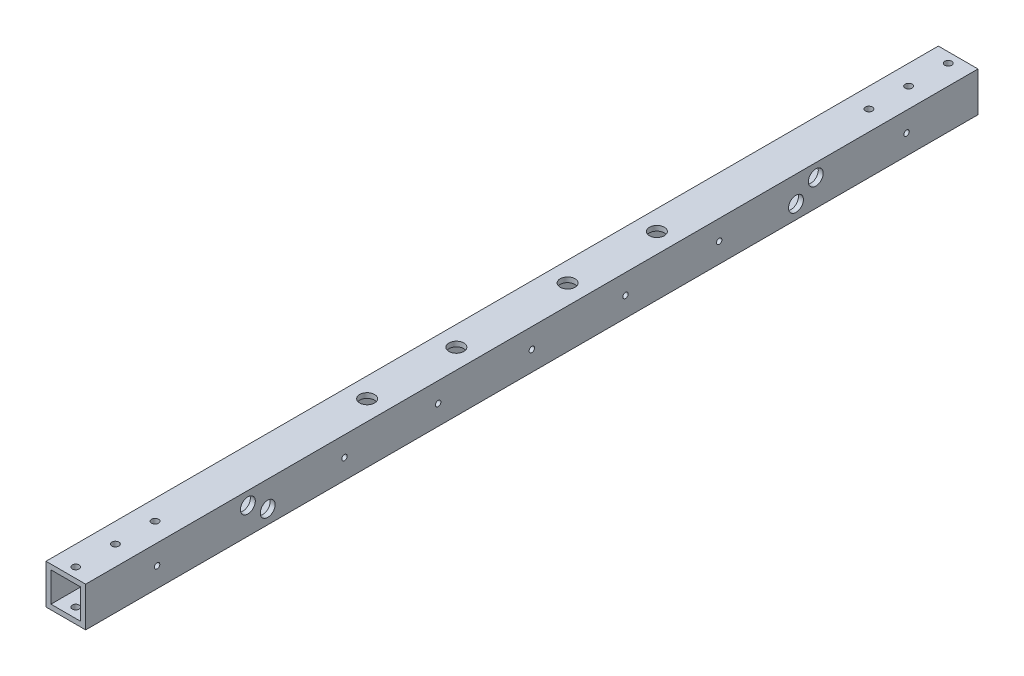
SolidWorks part; units mm, degrees
material "6061-T6 (SS)"
ref_plane "Front Plane" through (0, 0, 0) normal (0, 0, 1) x (1, 0, 0)
ref_plane "Top Plane" through (0, 0, 0) normal (0, 1, 0) x (1, 0, 0)
ref_plane "Right Plane" through (0, 0, 0) normal (1, 0, 0) x (0, 0, -1)
sketch "Sketch1" plane through (0, 0, 0) normal (0, 0, 1) x (1, 0, 0)
  line L1 (-12.7, -12.7) -> (12.7, -12.7)
  line L2 (-12.7, -12.7) -> (-12.7, 12.7)
  line L3 (-12.7, 12.7) -> (12.7, 12.7)
  line L4 (12.7, -12.7) -> (12.7, 12.7)
  line L5 (-12.7, -12.7) -> (12.7, 12.7) construction
  line L6 (-12.7, 12.7) -> (12.7, -12.7) construction
  point P0 (0, 0)
  dimension "D1" = 25.4
  dimension "D2" = 25.4
extrude "Extrude-Thin1" add sketch "Sketch1" along normal blind 571.5 thin thin type one direction reverse wall 3.175
hole_wizard "#8 Clearance Hole1" positions "3DSketch1" profile "Sketch3" hole size "#8" standard "ANSI Inch" end condition through all
sketch3d "3DSketch1"
  line L1 (12.7, 12.7, 0) -> (-12.7, 12.7, 0) construction
  line L6 (0, 12.7, 571.5) -> (0, 12.7, 0) construction
  line L7 (12.7, 12.7, 571.5) -> (-12.7, 12.7, 571.5) construction
  point P57 (0, 12.7, 6.35)
  point P59 (0, 12.7, 31.75)
  point P61 (0, 12.7, 57.15)
  point P63 (0, 12.7, 539.75)
  point P65 (0, 12.7, 514.35)
  point P67 (0, 12.7, 565.15)
  dimension "D1" = 25.4
  dimension "D2" = 25.4
  dimension "D3" = 6.35
  dimension "D4" = 25.4
  dimension "D5" = 25.4
  dimension "D6" = 6.35
sketch "Sketch3" plane through (0, 12.7, 565.15) normal (1, 0, 0) x (0, 0, 1)
  line L0 (0, 0) -> (0, 25.4)
  line L1 (0, 25.4) -> (2.2479, 25.4)
  line L2 (2.2479, 25.4) -> (2.2479, 0)
  line L5 (2.2479, 0) -> (0, 0)
  line L11 (0, -6.35) -> (0, 107.95) construction
  dimension "Thru Hole Dia." = 4.4958
  dimension "Thru Hole Depth" = 25.4
hole_wizard "#8-32 Tapped Hole1" positions "Sketch8" profile "Sketch9" tap size "#8-32" standard "ANSI Inch"
sketch "Sketch8" plane through (12.7, -82.55, 285.75) normal (1, 0, 0) x (0, 0, -1)
  point P0 (-240, 82.55)
  point P6 (-120, 82.55)
  point P9 (-60, 82.55)
  point P12 (0, 82.55)
  point P15 (60, 82.55)
  point P18 (120, 82.55)
  point P24 (240, 82.55)
sketch "Sketch9" plane through (12.7, 0, 525.75) normal (0, 1, 0) x (0, 0, -1)
  line L0 (0, 0) -> (0, 13.3314)
  line L1 (0, 13.3314) -> (1.7272, 12.2936)
  line L2 (1.7272, 12.2936) -> (1.7272, 0)
  line L3 (1.7272, 0) -> (0, 0)
  line L4 (0, 13.3314) -> (-1.7272, 12.2936) construction
  line L5 (0, -6.35) -> (0, 107.95) construction
  dimension "Tap Drill Dia." = 3.4544
  dimension "Tap Drill Depth" = 12.2936
  dimension "Drill Angle" = 118
hole_wizard "3/8 (0.375) Diameter Hole2" positions "Sketch12" profile "Sketch13" hole size "3/8" standard "ANSI Inch" end condition through all
sketch "Sketch12" plane through (-12.7, -82.55, 285.75) normal (1, 0, 0) x (0, 0, -1)
  point P0 (-181.864, 86.995)
  point P3 (-169.164, 78.74)
  point P6 (169.164, 78.74)
  point P9 (181.864, 86.995)
  point P12 (181.864, 57.15)
  point P15 (-181.864, 57.15)
sketch "Sketch13" plane through (-12.7, 4.445, 467.614) normal (0, 1, 0) x (0, 0, 1)
  line L0 (0, 0) -> (0, 25.4)
  line L1 (0, 25.4) -> (4.7625, 25.4)
  line L2 (4.7625, 25.4) -> (4.7625, 0)
  line L3 (4.7625, 0) -> (0, 0)
  line L4 (0, -6.35) -> (0, 107.95) construction
  dimension "Thru Hole Dia." = 9.525
  dimension "Thru Hole Depth" = 25.4
hole_wizard "3/8 (0.375) Diameter Hole3" positions "Sketch14" profile "Sketch15" hole size "3/8" standard "ANSI Inch" end condition through all
sketch "Sketch14" plane through (-346.075, 12.7, 285.75) normal (0, 1, 0) x (0, 0, 1)
  point P9 (-92.7735, 346.075)
  point P12 (-35.6235, 346.075)
  point P18 (35.6235, 346.075)
  point P21 (92.7735, 346.075)
  point P24 (-19.05, -346.775)
  point P27 (53.975, -346.775)
  point P30 (127, -346.775)
  point P42 (-381, -114.3)
  point P45 (-381, -130.175)
  point P48 (-381, -146.05)
  point P55 (-381, 114.3)
  point P58 (-381, 98.425)
  point P61 (-381, 82.55)
sketch "Sketch15" plane through (0, 12.7, 192.9765) normal (1, 0, 0) x (0, 0, 1)
  line L0 (0, 0) -> (0, 25.4)
  line L1 (0, 25.4) -> (4.7625, 25.4)
  line L2 (4.7625, 25.4) -> (4.7625, 0)
  line L3 (4.7625, 0) -> (0, 0)
  line L4 (0, -6.35) -> (0, 107.95) construction
  dimension "Thru Hole Dia." = 9.525
  dimension "Thru Hole Depth" = 25.4
